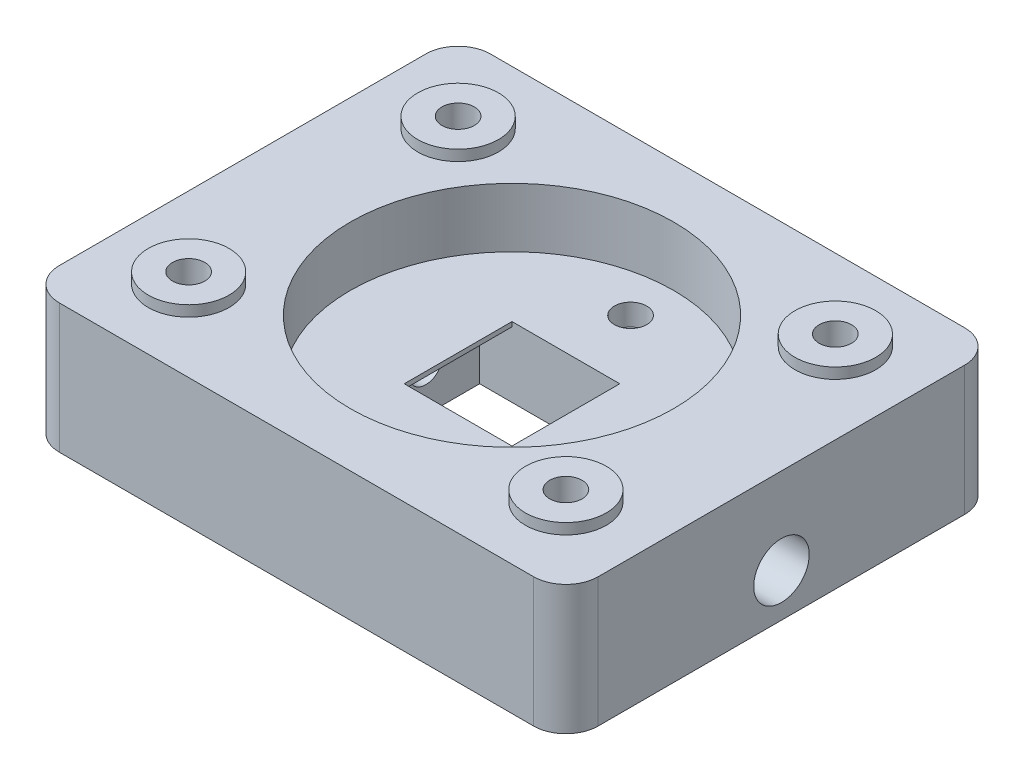
SolidWorks part; units mm, degrees
other "BodyCell"
ref_plane "Front Plane" through (0, 0, 0) normal (0, 0, 1) x (1, 0, 0)
ref_plane "Top Plane" through (0, 0, 0) normal (0, 1, 0) x (1, 0, 0)
ref_plane "Right Plane" through (0, 0, 0) normal (1, 0, 0) x (0, 0, -1)
sketch "Sketch1" plane through (0, 0, 0) normal (0, 1, 0) x (1, 0, 0)
  line L1 (25, -20) -> (-25, -20)
  line L2 (25, -20) -> (25, 20)
  line L3 (25, 20) -> (-25, 20)
  line L4 (-25, -20) -> (-25, 20)
  line L5 (25, -20) -> (-25, 20) construction
  line L6 (25, 20) -> (-25, -20) construction
  point P0 (0, 0)
  dimension "D1" = 50
  dimension "D2" = 40
extrude "Body" add sketch "Sketch1" along normal blind 12
fillet "FilletBody" radius 3 4 edges at (-25, 6, -20) (25, 6, -20) (25, 6, 20) (-25, 6, 20)
sketch "Sketch3" plane through (0, 12, 0) normal (0, 1, 0) x (1, 0, 0)
  line L0 (-25, 17) -> (-25, -17) construction
  line L1 (22, 20) -> (-22, 20) construction
  line L2 (-38.934, 0) -> (38.0552, 0) construction
  line L3 (0, 29.5616) -> (0, -31.3312) construction
  circle A0 centre (-17.5, 12.5) radius 3.75
  circle A1 centre (17.5, 12.5) radius 3.75
  circle A2 centre (17.5, -12.5) radius 3.75
  circle A3 centre (-17.5, -12.5) radius 3.75
  dimension "D1" = 7.5
  dimension "D2" = 7.5
  dimension "D3" = 7.5
extrude "Bolt extrude" add sketch "Sketch3" along normal blind 1
sketch "Sketch4" plane through (0, 13, 0) normal (0, 1, 0) x (1, 0, 0)
  line L2 (-40.7589, 0) -> (37.9331, 0) construction
  line L3 (-55, 0) -> (55, 0) construction
  line L4 (0, 29.2624) -> (0, -30.4072) construction
  circle A0 centre (-17.5, 12.5) radius 1.5
  circle A1 centre (17.5, 12.5) radius 1.5
  circle A2 centre (17.5, -12.5) radius 1.5
  circle A3 centre (-17.5, -12.5) radius 1.5
  dimension "D1" = 3
extrude "Bolt" cut sketch "Sketch4" against normal blind 16 and the other way blind 10
sketch "Sketch41" plane through (-25, 0, 0) normal (-1, 0, 0) x (0, 0, 1)
  line L0 (0, -55) -> (0, 55) construction
  line L1 (55, 0) -> (-55, 0) construction
  circle A0 centre (0, 4) radius 1.575
  dimension "D1" = 3.15
  dimension "D2" = 4
extrude "Channel1" cut sketch "Sketch41" against normal blind 57
sketch "Sketch42" plane through (-25, 0, 0) normal (-1, 0, 0) x (0, 0, 1)
  circle A0 centre (0, 4) radius 2.575
  dimension "D1" = 5.15
extrude "Inlet" cut sketch "Sketch42" against normal blind 5
sketch "Sketch43" plane through (25, 0, 0) normal (1, 0, 0) x (0, 0, -1)
  circle A0 centre (0, 4) radius 2.575 construction
  circle A1 centre (0, 4) radius 2.575
extrude "Outlet" cut sketch "Sketch43" against normal blind 5
sketch "Sketch44" plane through (0, 12, 0) normal (0, 1, 0) x (1, 0, 0)
  circle A0 centre (0, 0) radius 15
  dimension "D1" = 30
extrude "Window" cut sketch "Sketch44" against normal blind 5.5
sketch "Sketch45" plane through (0, 0, 0) normal (0, -1, 0) x (1, 0, 0)
  line L1 (8, -5) -> (-8, -5)
  line L2 (8, -5) -> (8, 5)
  line L3 (8, 5) -> (-8, 5)
  line L4 (-8, -5) -> (-8, 5)
  line L5 (8, -5) -> (-8, 5) construction
  line L6 (8, 5) -> (-8, -5) construction
  point P0 (0, 0)
  dimension "D1" = 10
  dimension "D2" = 16
extrude "FlowCh" cut sketch "Sketch45" against normal blind 5.575
sketch "Sketch46" plane through (0, 6.5, 0) normal (0, 1, 0) x (1, 0, 0)
  line L1 (5, -5) -> (-5, -5)
  line L2 (5, -5) -> (5, 5)
  line L3 (5, 5) -> (-5, 5)
  line L4 (-5, -5) -> (-5, 5)
  line L5 (5, -5) -> (-5, 5) construction
  line L6 (5, 5) -> (-5, -5) construction
  point P0 (0, 0)
  dimension "D1" = 10
  dimension "D2" = 10
extrude "Window_hole" cut sketch "Sketch46" against normal blind 16
sketch "Sketch49" plane through (0, 6.5, 0) normal (0, 1, 0) x (1, 0, 0)
  line L0 (-7.15, 0) -> (7.15, 0) construction
  circle A5 centre (0, 11) radius 1.5
  circle A7 centre (0, -11) radius 1.5
  circle A9 centre (-11, 0) radius 1.5 [skipped]
  circle A10 centre (11, 0) radius 1.5 [skipped]
  point P14 (0, 0)
  dimension "D3" = 3
  dimension "D1" = 11
  dimension "D2" = 4
extrude "FixHoles" cut sketch "Sketch49" against normal blind 2
sketch "Sketch50" plane through (0, 0, 0) normal (0, -1, 0) x (1, 0, 0)
  line L0 (-8, 7) -> (8, 7)
  line L1 (8, 5) -> (-8, 5) construction
  line L2 (10, 5) -> (10, -5)
  line L3 (8, -5) -> (8, 5) construction
  line L4 (0, 12.2512) -> (0, -10.9162) construction
  line L5 (-29.6034, 0) -> (30.3234, 0) construction
  line L6 (7.15, 0) -> (-7.15, 0) construction
  line L7 (-10, 5) -> (-10, -5)
  line L8 (-8, -7) -> (8, -7)
  line L9 (14, 5) -> (14, -5)
  line L10 (-8, -11) -> (8, -11)
  line L11 (-14, 5) -> (-14, -5)
  line L12 (-8, 11) -> (8, 11)
  arc A0 (8, 7) -> (10, 5) centre (8, 5) cw
  arc A1 (-8, 7) -> (-10, 5) centre (-8, 5) ccw
  arc A2 (8, -7) -> (10, -5) centre (8, -5) ccw
  arc A3 (-8, -7) -> (-10, -5) centre (-8, -5) cw
  arc A4 (8, -11) -> (14, -5) centre (8, -5) ccw
  arc A5 (-8, -11) -> (-14, -5) centre (-8, -5) cw
  arc A6 (-8, 11) -> (-14, 5) centre (-8, 5) ccw
  arc A7 (8, 11) -> (14, 5) centre (8, 5) cw
  dimension "D1" = 2
  dimension "D2" = 2
  dimension "D3" = 4
extrude "Gasket" cut sketch "Sketch50" against normal blind 1 contours A7 L12 A6 L11 A5 L10 A4 L9 L8 A3 L7 A1 L0 A0 L2 A2 region at (13.6439, 0, 0)
chamfer "Chamfer_flow" distance 3 distance2 0.5 2 edges at (5, 5.575, 0) (-5, 5.575, 0) first distance on face at (6.8, 5.575, 0) first distance on face at (-6.8, 5.575, 0)
